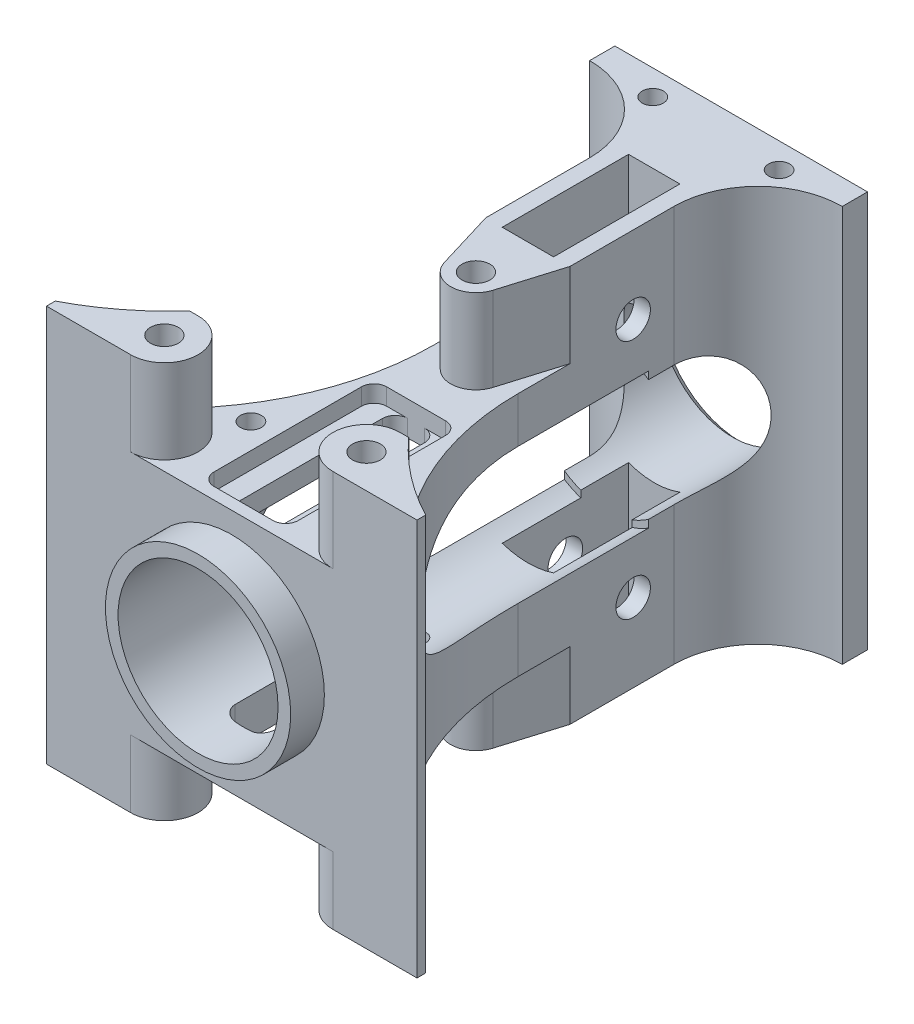
SolidWorks part; units mm, degrees
material "6061 合金"
ref_plane "前视基准面" through (0, 0, 0) normal (0, 0, 1) x (1, 0, 0)
ref_plane "上视基准面" through (0, 0, 0) normal (0, 1, 0) x (1, 0, 0)
ref_plane "右视基准面" through (0, 0, 0) normal (1, 0, 0) x (0, 0, -1)
sketch "草图1" plane through (0, 0, 0) normal (0, 0, 1) x (1, 0, 0)
  line L1 (-24, -15.5) -> (24, -15.5)
  line L2 (-24, -15.5) -> (-24, 15.5)
  line L3 (-24, 15.5) -> (24, 15.5)
  line L4 (24, -15.5) -> (24, 15.5)
  line L5 (0, 15.5) -> (0, -15.5) construction
  line L6 (-24, 0) -> (24, 0) construction
  point P0 (0, 0)
  dimension "D1" = 48
  dimension "D2" = 31
extrude "凸台-拉伸1" add sketch "草图1" along normal blind 39 and the other way blind 31.5
sketch "草图2" plane through (0, 0, -31.5) normal (0, 0, -1) x (-1, 0, 0)
  circle A0 centre (0, 0) radius 8.75
  dimension "D1" = 17.5
extrude "切除-拉伸1" cut sketch "草图2" against normal blind 135
sketch "草图4" plane through (0, 0, 39) normal (0, 0, 1) x (1, 0, 0)
  circle A0 centre (0, 0) radius 9.5
  dimension "D1" = 19
extrude "切除-拉伸2" cut sketch "草图4" against normal offset from surface (54.5 mm away) 16 up to face at (-8.75, 0, -31.5)
sketch "草图5" plane through (0, 15.5, 0) normal (0, 1, 0) x (1, 0, 0)
  line L0 (-36.5, 0) -> (36.5, 0) construction
  circle A0 centre (36.5, 0) radius 30 construction
  circle A1 centre (-36.5, 0) radius 30 construction
  circle A2 centre (36.5, 0) radius 31.5
  circle A3 centre (-36.5, 0) radius 31.5
  point P4 (0, 0)
  dimension "D1" = 60
  dimension "D2" = 73
  dimension "D3" = 1.5
extrude "切除-拉伸3" cut sketch "草图5" against normal blind 86
sketch "草图8" plane through (0, 0, 39) normal (0, 0, 1) x (1, 0, 0)
  circle A0 centre (0, 0) radius 10.5
  dimension "D1" = 21
extrude "切除-拉伸5" cut sketch "草图8" against normal blind 10 flip side to cut
ref_plane "基准面1" through (22, 0, 0) normal (1, 0, 0) x (0, 0, -1)
sketch "配合草图" plane through (0, 15.5, 0) normal (0, 1, 0) x (1, 0, 0)
  line L0 (-36.5, 0) -> (36.5, 0) construction
  circle A0 centre (36.5, 0) radius 30
  circle A1 centre (-36.5, 0) radius 30
  point P4 (0, 0)
  dimension "D2" = 60
  dimension "D1" = 73
sketch "草图12" plane through (0, 15.5, 0) normal (0, 1, 0) x (1, 0, 0)
  line L7 (0, 0) -> (0, 33.1497) construction
  line L16 (-5, 0) -> (-5, 18.5)
  line L17 (-5, 0) -> (-24, 28.9137)
  line L20 (-24, 28.9137) -> (-24, 31.5)
  line L22 (-24, 31.5) -> (-15, 31.5)
  line L25 (-15, 31.5) -> (-15, 28.5)
  line L32 (15, 28.5) -> (23.0263, 27) construction
  line L33 (15, 31.5) -> (15, 28.5)
  line L34 (24, 31.5) -> (15, 31.5)
  line L35 (24, 28.9137) -> (24, 31.5)
  line L36 (5, 0) -> (24, 28.9137)
  line L37 (5, 0) -> (5, 18.5)
  arc A5 (-24, -28.9137) -> (-24, 28.9137) centre (-36.5, 0) ccw construction
  arc A8 (-15, 28.5) -> (-5, 18.5) centre (-15, 18.5) cw
  arc A9 (15, 28.5) -> (5, 18.5) centre (15, 18.5) ccw
  dimension "D3" = 10
  dimension "D1" = 15
  dimension "D2" = 3
extrude "切除-拉伸6" cut sketch "草图12" against normal blind 50
sketch "草图14" plane through (22, 0, 0) normal (1, 0, 0) x (0, 0, -1)
  line L0 (31.5, -15.5) -> (31.5, 15.5) construction
  line L1 (-31.5, -15.5) -> (31.5, -15.5)
  line L2 (-31.5, -15.5) -> (-31.5, 15.5)
  line L3 (-31.5, 15.5) -> (31.5, 15.5)
  line L4 (31.5, -15.5) -> (31.5, 15.5)
  line L5 (0, 15.5) -> (0, -15.5) construction
  line L6 (-31.5, 0) -> (31.5, 0) construction
  line L7 (-29, 15.5) -> (-28.9137, 15.5) construction
  point P0 (0, 0)
extrude "切除-拉伸7" cut sketch "草图14" along normal blind 50
mirror "镜向1" about plane through (0, 0, 0) normal (1, 0, 0) of "切除-拉伸7"
sketch "草图15" plane through (-22, 0, 0) normal (-1, 0, 0) x (0, 0, 1)
  line L0 (29, 15.5) -> (38, 15.5)
  line L1 (38, 15.5) -> (38, -15.5)
  line L2 (38, -15.5) -> (29, -15.5)
  line L3 (29, 15.5) -> (29, -15.5)
  dimension "D1" = 9
extrude "凸台-拉伸2" add sketch "草图15" against normal blind 2
sketch "草图16" plane through (-22, 0, 0) normal (-1, 0, 0) x (0, 0, 1)
  line L0 (30.2, -7) -> (33.1, -7) construction
  line L1 (30.2, 13) -> (35.3014, 13) construction
  line L2 (29, -7) -> (38, -7)
  line L3 (29, 13) -> (38, 13)
  line L5 (38, -15.5) -> (38, 15.5) construction
  line L6 (29, -7) -> (29, -15.5)
  line L7 (38, -15.5) -> (27.9643, -15.5) construction
  line L8 (29, -15.5) -> (38, -15.5)
  line L9 (38, -15.5) -> (38, -7)
  line L10 (29, 13) -> (29, 15.5)
  line L11 (27.9643, 15.5) -> (38, 15.5) construction
  line L12 (29, 15.5) -> (38, 15.5)
  line L13 (38, 15.5) -> (38, 13)
  line L14 (29, 15.5) -> (29, -15.5) construction
extrude "切除-拉伸8" cut sketch "草图16" against normal blind 3
fillet "圆角1" radius 3.5 2 edges at (-21, -7, 38) (-21, 13, 38)
sketch "草图17" plane through (-22, 0, 0) normal (-1, 0, 0) x (0, 0, 1)
  line L0 (29, 13) -> (34.5, 13) construction
  line L2 (34.5, -7) -> (29, -7) construction
  circle A4 centre (35.2, 9.8) radius 1.55
  circle A5 centre (35.2, -3.8) radius 1.55
  dimension "D1" = 3.1
  dimension "D2" = 3.2
  dimension "D3" = 35.2
  dimension "D4" = 35.2
  dimension "D5" = 3.2
extrude "切除-拉伸9" cut sketch "草图17" against normal blind 3
fillet "圆角2" [suppressed] radius 0.5
sketch "草图18" plane through (22, 0, 0) normal (1, 0, 0) x (0, 0, -1)
  line L4 (-38, 9.5) -> (-38, -3.5)
  line L5 (-34.5, -7) -> (-29, -7)
  line L6 (-29, -7) -> (-29, 13)
  line L7 (-29, 13) -> (-34.5, 13)
  line L8 (-38, 9.5) -> (-38, -3.5)
  line L9 (-34.5, -7) -> (-29, -7)
  line L10 (-29, -7) -> (-29, 13)
  line L11 (-29, 13) -> (-34.5, 13)
  circle A0 centre (-35.2, -3.8) radius 1.55 construction
  circle A1 centre (-35.2, 9.8) radius 1.55 construction
  arc A2 (-38, -3.5) -> (-34.5, -7) centre (-34.5, -3.5) ccw
  arc A3 (-34.5, 13) -> (-38, 9.5) centre (-34.5, 9.5) ccw
  arc A4 (-38, -3.5) -> (-34.5, -7) centre (-34.5, -3.5) ccw
  arc A5 (-34.5, 13) -> (-38, 9.5) centre (-34.5, 9.5) ccw
  circle A6 centre (-35.2, -3.8) radius 1.55
  circle A7 centre (-35.2, 9.8) radius 1.55
  dimension "D1" = 0
extrude "凸台-拉伸3" add sketch "草图18" against normal blind 2
sketch "草图19" plane through (0, 15.5, 0) normal (0, 1, 0) x (1, 0, 0)
  line L7 (5, 0) -> (5, 18.5)
  line L8 (-22, -27.9643) -> (-22, -29)
  line L9 (-22, -29) -> (22, -29)
  line L10 (22, -29) -> (22, -27.9643)
  line L13 (15, 31.5) -> (-15, 31.5)
  line L14 (-15, 31.5) -> (-15, 28.5)
  line L15 (-5, 18.5) -> (-5, 0)
  line L16 (-22, -27.9643) -> (-22, -29)
  line L17 (-22, -29) -> (22, -29)
  line L18 (22, -29) -> (22, -27.9643)
  line L21 (15, 31.5) -> (-15, 31.5)
  line L22 (-15, 31.5) -> (-15, 28.5)
  line L23 (-5, 18.5) -> (-5, 0)
  line L24 (5, 0) -> (5, 18.5)
  line L25 (15, 28.5) -> (15, 31.5)
  line L26 (15, 28.5) -> (15, 31.5)
  arc A4 (5, 0) -> (22, -27.9643) centre (36.5, 0) ccw
  arc A5 (15, 28.5) -> (5, 18.5) centre (15, 18.5) ccw
  arc A6 (-5, 18.5) -> (-15, 28.5) centre (-15, 18.5) ccw
  arc A7 (-22, -27.9643) -> (-5, 0) centre (-36.5, 0) ccw
  arc A8 (5, 0) -> (22, -27.9643) centre (36.5, 0) ccw
  arc A10 (-5, 18.5) -> (-15, 28.5) centre (-15, 18.5) ccw
  arc A11 (-22, -27.9643) -> (-5, 0) centre (-36.5, 0) ccw
  arc A12 (15, 28.5) -> (5, 18.5) centre (15, 18.5) ccw
  dimension "D1" = 0
extrude "凸台-拉伸4" add sketch "草图19" along normal blind 8
sketch "草图20" plane through (0, 0, 0) normal (1, 0, 0) x (0, 0, -1)
  circle A0 centre (13.67, 14.3) radius 2.05
  dimension "D3" = 4.1
  dimension "D1" = 13.67
  dimension "D2" = 14.3
extrude "切除-拉伸10" cut sketch "草图20" against normal mid plane 78
sketch "草图21" plane through (0, -15.5, 0) normal (0, -1, 0) x (1, 0, 0)
  line L8 (22, 29) -> (-22, 29)
  line L9 (-22, 29) -> (-22, 27.9643)
  line L10 (-5, 0) -> (-5, -18.5)
  line L11 (-15, -28.5) -> (-15, -31.5)
  line L12 (-15, -31.5) -> (15, -31.5)
  line L13 (15, -31.5) -> (15, -28.5)
  line L14 (5, -18.5) -> (5, 0)
  line L15 (22, 27.9643) -> (22, 29)
  line L16 (22, 29) -> (-22, 29)
  line L17 (-22, 29) -> (-22, 27.9643)
  line L18 (-5, 0) -> (-5, -18.5)
  line L19 (-15, -28.5) -> (-15, -31.5)
  line L20 (-15, -31.5) -> (15, -31.5)
  line L21 (15, -31.5) -> (15, -28.5)
  line L22 (5, -18.5) -> (5, 0)
  line L23 (22, 27.9643) -> (22, 29)
  arc A4 (-5, 0) -> (-22, 27.9643) centre (-36.5, 0) ccw
  arc A5 (-15, -28.5) -> (-5, -18.5) centre (-15, -18.5) ccw
  arc A6 (5, -18.5) -> (15, -28.5) centre (15, -18.5) ccw
  arc A7 (22, 27.9643) -> (5, 0) centre (36.5, 0) ccw
  arc A8 (-5, 0) -> (-22, 27.9643) centre (-36.5, 0) ccw
  arc A9 (-15, -28.5) -> (-5, -18.5) centre (-15, -18.5) ccw
  arc A10 (5, -18.5) -> (15, -28.5) centre (15, -18.5) ccw
  arc A11 (22, 27.9643) -> (5, 0) centre (36.5, 0) ccw
  dimension "D1" = 0
extrude "凸台-拉伸5" add sketch "草图21" along normal blind 8.1
mirror "镜向6" about plane through (0, 0, 0) normal (0, 1, 0) of "切除-拉伸10"
sketch "草图23" plane through (0, 0, 0) normal (1, 0, 0) x (0, 0, -1)
  line L0 (18.5, -23.6) -> (0, -23.6) construction
  line L1 (6.17, -23.6) -> (21.17, -23.6)
  line L2 (6.17, -23.6) -> (6.17, 52.2)
  line L3 (6.17, 52.2) -> (21.17, 52.2)
  line L4 (21.17, -23.6) -> (21.17, 52.2)
  line L5 (13.67, 52.2) -> (13.67, -23.6) construction
  line L6 (6.17, 14.3) -> (21.17, 14.3) construction
  point P0 (13.67, 14.3)
  dimension "D1" = 15
extrude "切除-拉伸11" cut sketch "草图23" against normal mid plane 6.1
sketch "草图24" plane through (0, 23.5, 0) normal (0, 1, 0) x (1, 0, 0)
  line L0 (-7.5, 28.5) -> (7.5, 28.5) construction
  line L1 (0, 28.5) -> (0, 0) construction
  line L2 (15, 31.5) -> (-15, 31.5) construction
  point P3 (0, 28.5)
  dimension "D1" = 3
  dimension "D2" = 15
hole_wizard "M3 螺纹孔1" positions "草图25" profile "草图26" tap size "M3" standard "GB"
sketch "草图25" plane through (0, 23.5, 0) normal (0, 1, 0) x (1, 0, 0)
  point P0 (-7.5, 28.5)
  point P3 (7.5, 28.5)
sketch "草图26" plane through (-7.5, 23.5, -28.5) normal (1, 0, 0) x (0, 0, 1)
  line L0 (0, 0) -> (0, 8.2511)
  line L1 (0, 8.2511) -> (1.25, 7.5)
  line L2 (1.25, 7.5) -> (1.25, 0)
  line L5 (1.25, 0) -> (0, 0)
  line L10 (0, 8.2511) -> (-1.25, 7.5) construction
  line L11 (0, -6.35) -> (0, 107.95) construction
  dimension "螺纹孔钻头直径" = 2.5
  dimension "螺纹孔钻头深度" = 7.5
  dimension "导头角度" = 118
cosmetic thread "孔螺蚊线1"
cosmetic thread "孔螺蚊线2"
sketch "草图27" plane through (0, 23.5, 0) normal (0, 1, 0) x (1, 0, 0)
  line L0 (-12, -25) -> (12, -25) construction
  line L1 (0, 0) -> (0, -25) construction
  line L2 (-22, -29) -> (22, -29) construction
  point P3 (0, -25)
  dimension "D1" = 4
  dimension "D2" = 24
hole_wizard "M4 螺纹孔2" positions "草图28" profile "草图29" tap size "M4" standard "GB"
sketch "草图28" plane through (0, 23.5, 0) normal (0, 1, 0) x (1, 0, 0)
  point P0 (-12, -25)
  point P3 (12, -25)
sketch "草图29" plane through (-12, 23.5, 25) normal (1, 0, 0) x (0, 0, 1)
  line L0 (0, 0) -> (0, 11.0914)
  line L1 (0, 11.0914) -> (1.65, 10.1)
  line L2 (1.65, 10.1) -> (1.65, 0)
  line L5 (1.65, 0) -> (0, 0)
  line L10 (0, 11.0914) -> (-1.65, 10.1) construction
  line L11 (0, -6.35) -> (0, 107.95) construction
  dimension "螺纹孔钻头直径" = 3.3
  dimension "螺纹孔钻头深度" = 10.1
  dimension "导头角度" = 118
cosmetic thread "孔螺蚊线3"
cosmetic thread "孔螺蚊线4"
sketch "草图30" plane through (0, 23.5, 0) normal (0, 1, 0) x (1, 0, 0)
  line L0 (-10.5, -29) -> (10.5, -29) construction
  line L1 (-12, -21) -> (-13.0213, -21)
  line L2 (12, -21) -> (13.0213, -21)
  line L3 (-12, -29) -> (12, -29)
  line L4 (-5, 0) -> (5, 0)
  arc A0 (-12, -29) -> (-12, -21) centre (-12, -25) ccw
  arc A1 (12, -21) -> (12, -29) centre (12, -25) ccw
  arc A2 (-22, -27.9643) -> (-5, 0) centre (-36.5, 0) ccw construction
  arc A3 (5, 0) -> (22, -27.9643) centre (36.5, 0) ccw construction
  arc A4 (5, 0) -> (13.0213, -21) centre (36.5, 0) ccw
  arc A5 (-13.0213, -21) -> (-5, 0) centre (-36.5, 0) ccw
extrude "切除-拉伸12" cut sketch "草图30" against normal blind 10
hole_wizard "M3 螺纹孔2" positions "草图31" profile "草图32" tap size "M3" standard "GB"
sketch "草图31" plane through (0, -23.6, 0) normal (0, -1, 0) x (-1, 0, 0)
  point P6 (-7.5, 28.5)
  point P9 (7.5, 28.5)
sketch "草图32" plane through (7.5, -23.6, -28.5) normal (1, 0, 0) x (0, 0, -1)
  line L0 (0, 0) -> (0, 8.2511)
  line L1 (0, 8.2511) -> (1.25, 7.5)
  line L2 (1.25, 7.5) -> (1.25, 0)
  line L5 (1.25, 0) -> (0, 0)
  line L10 (0, 8.2511) -> (-1.25, 7.5) construction
  line L11 (0, -6.35) -> (0, 107.95) construction
  dimension "螺纹孔钻头直径" = 2.5
  dimension "螺纹孔钻头深度" = 7.5
  dimension "导头角度" = 118
cosmetic thread "孔螺蚊线5"
cosmetic thread "孔螺蚊线6"
extrude "切除-拉伸13" cut sketch "草图30<2>" along normal blind 8 from surface starting at face at (7.5, -23.6, -29.75)
sketch "草图30<2>" plane through (0, 23.5, 0) normal (0, 1, 0) x (1, 0, 0) same geometry as "草图30"
sketch "草图33" plane through (5, 0, 0) normal (1, 0, 0) x (0, 0, -1)
  line L0 (0, -15.6) -> (6.17, -15.6)
  line L1 (6.17, -15.6) -> (6.17, -23.6)
  line L2 (18.5, -23.6) -> (0, -23.6) construction
  line L3 (6.17, -23.6) -> (0, -23.6)
  line L4 (0, -23.6) -> (0, -15.6)
  line L5 (0, 13.5) -> (0, 23.5)
  line L6 (0, 23.5) -> (6.17, 23.5)
  line L8 (0, 23.5) -> (18.5, 23.5) construction
  line L9 (6.17, 23.5) -> (6.17, 13.5)
  line L10 (6.17, 13.5) -> (0, 13.5)
  line L11 (6.17, -8.9971) -> (6.17, -23.6) construction
extrude "切除-拉伸14" cut sketch "草图33" against normal blind 36
chamfer "倒角1" distance 1 angle 45 1 edges at (-8.75, 0, -31.5)
hole_wizard "M4 螺纹孔4" positions "草图34" profile "草图35" tap size "M4" standard "GB"
sketch "草图34" plane through (0, -23.6, 0) normal (0, -1, 0) x (-1, 0, 0)
  point P0 (-12, -25)
  point P3 (12, -25)
sketch "草图35" plane through (12, -23.6, 25) normal (1, 0, 0) x (0, 0, -1)
  line L0 (0, 0) -> (0, 11.0914)
  line L1 (0, 11.0914) -> (1.65, 10.1)
  line L2 (1.65, 10.1) -> (1.65, 0)
  line L5 (1.65, 0) -> (0, 0)
  line L10 (0, 11.0914) -> (-1.65, 10.1) construction
  line L11 (0, -6.35) -> (0, 107.95) construction
  dimension "螺纹孔钻头直径" = 3.3
  dimension "螺纹孔钻头深度" = 10.1
  dimension "导头角度" = 118
cosmetic thread "孔螺蚊线9"
cosmetic thread "孔螺蚊线10"
sketch "草图36" plane through (0, 13.5, 0) normal (0, 1, 0) x (1, 0, 0)
  line L0 (0, 0) -> (0, -17.35) construction
  line L1 (-5, -27.6) -> (5, -27.6)
  line L2 (-5, -27.6) -> (-5, -7.1)
  line L3 (-5, -7.1) -> (5, -7.1)
  line L4 (5, -27.6) -> (5, -7.1)
  line L5 (-5, -27.6) -> (5, -7.1) construction
  line L6 (-5, -7.1) -> (5, -27.6) construction
  line L7 (-12, -29) -> (12, -29) construction
  point P3 (0, -17.35)
  dimension "D1" = 10
  dimension "D2" = 20.5
  dimension "D3" = 1.4
extrude "切除-拉伸15" cut sketch "草图36" against normal blind 2
sketch "草图37" plane through (0, 11.5, 0) normal (0, 1, 0) x (1, 0, 0)
  line L0 (5, -7.1) -> (-5, -7.1) construction
  line L1 (-2.5, -27.6) -> (2.5, -27.6)
  line L2 (-2.5, -27.6) -> (-2.5, -7.1)
  line L3 (-2.5, -7.1) -> (2.5, -7.1)
  line L4 (2.5, -27.6) -> (2.5, -7.1)
  line L5 (-2.5, -27.6) -> (2.5, -7.1) construction
  line L6 (-2.5, -7.1) -> (2.5, -27.6) construction
  line L7 (0, 0) -> (0, -17.35) construction
  line L8 (-5, -27.6) -> (5, -27.6) construction
  point P0 (0, -17.35)
  dimension "D1" = 5
extrude "切除-拉伸17" cut sketch "草图37" against normal blind 72
fillet "圆角3" radius 1.5 8 edges at (-2.5, 10.3326, 27.6) (-5, 12.5, 27.6) (-2.5, 10.3326, 7.1) (-5, 12.5, 7.1) (2.5, 10.3326, 7.1) (2.5, 10.3326, 27.6) (5, 12.5, 27.6) (5, 12.5, 7.1)
sketch "草图38" plane through (0, -15.6, 0) normal (0, -1, 0) x (1, 0, 0)
  line L0 (-2.5, 27.6) -> (2.5, 27.6) construction
  line L1 (-5, 7.1) -> (5, 7.1)
  line L2 (-5, 7.1) -> (-5, 27.6)
  line L3 (-5, 27.6) -> (5, 27.6)
  line L4 (5, 7.1) -> (5, 27.6)
  line L5 (-5, 7.1) -> (5, 27.6) construction
  line L6 (-5, 27.6) -> (5, 7.1) construction
  line L7 (2.5, 7.1) -> (-2.5, 7.1) construction
  line L8 (0, 17.35) -> (0, 0) construction
  point P0 (0, 17.35)
  dimension "D1" = 10
extrude "切除-拉伸18" cut sketch "草图38" against normal blind 2
fillet "圆角4" radius 1.5 8 edges at (-2.5, -11.3826, 7.1) (-2.5, -11.3826, 27.6) (2.5, -11.3826, 7.1) (2.5, -11.3826, 27.6) (5, -14.6, 27.6) (5, -14.6, 7.1) (-5, -14.6, 27.6) (-5, -14.6, 7.1)
sketch "草图39" plane through (0, 13.5, 0) normal (0, 1, 0) x (1, 0, 0)
  line L0 (-8, -18.7232) -> (8, -18.7232) construction
  line L1 (0, 0) -> (0, -18.7232) construction
  line L2 (5, -26.1) -> (5, -8.6) construction
  circle A0 centre (8, -18.7232) radius 1.55 construction
  arc A12 (5, 0) -> (13.0213, -21) centre (36.5, 0) ccw construction
  dimension "D1" = 3.1
  dimension "D3" = 2.6
  dimension "D2" = 3
hole_wizard "M3 螺纹孔3" positions "草图40" profile "草图41" tap size "M3" standard "GB"
sketch "草图40" plane through (0, 13.5, 0) normal (0, 1, 0) x (1, 0, 0)
  point P0 (-8, -18.7232)
  point P3 (8, -18.7232)
sketch "草图41" plane through (-8, 13.5, 18.7232) normal (1, 0, 0) x (0, 0, 1)
  line L0 (0, 0) -> (0, 6.2511)
  line L1 (0, 6.2511) -> (1.25, 5.5)
  line L2 (1.25, 5.5) -> (1.25, 0)
  line L5 (1.25, 0) -> (0, 0)
  line L10 (0, 6.2511) -> (-1.25, 5.5) construction
  line L11 (0, -6.35) -> (0, 107.95) construction
  dimension "螺纹孔钻头直径" = 2.5
  dimension "螺纹孔钻头深度" = 5.5
  dimension "导头角度" = 118
cosmetic thread "孔螺蚊线11"
cosmetic thread "孔螺蚊线12"
hole_wizard "M3 螺纹孔4" positions "草图43" profile "草图44" tap size "M3" standard "GB"
sketch "草图43" plane through (0, -15.6, 0) normal (0, -1, 0) x (-1, 0, 0)
  point P0 (8, -18.7232)
  point P3 (-8, -18.7232)
sketch "草图44" plane through (-8, -15.6, 18.7232) normal (1, 0, 0) x (0, 0, -1)
  line L0 (0, 0) -> (0, 6.2511)
  line L1 (0, 6.2511) -> (1.25, 5.5)
  line L2 (1.25, 5.5) -> (1.25, 0)
  line L5 (1.25, 0) -> (0, 0)
  line L10 (0, 6.2511) -> (-1.25, 5.5) construction
  line L11 (0, -6.35) -> (0, 107.95) construction
  dimension "螺纹孔钻头直径" = 2.5
  dimension "螺纹孔钻头深度" = 5.5
  dimension "导头角度" = 118
cosmetic thread "孔螺蚊线13"
cosmetic thread "孔螺蚊线14"
sketch "草图45" plane through (0, 13.5, 0) normal (0, 1, 0) x (1, 0, 0)
  line L0 (22, -29) -> (22, -34.5) construction
  line L1 (-22, -29) -> (22, -29)
  line L2 (-22, -29) -> (-22, -44)
  line L3 (-22, -44) -> (22, -44)
  line L4 (22, -29) -> (22, -44)
  dimension "D1" = 15
extrude "切除-拉伸19" cut sketch "草图45" against normal blind 37
sketch "草图47" plane through (0, -15.6, 0) normal (0, -1, 0) x (1, 0, 0)
  line L0 (-5, -6.17) -> (-2.8716, 0.8684)
  line L1 (2.8716, 0.8684) -> (5, -6.17)
  line L2 (-5, -6.17) -> (5, -6.17)
  arc A0 (2.8716, 0.8684) -> (-2.8716, 0.8684) centre (0, 0) ccw
  dimension "D1" = 6
extrude "凸台-拉伸6" add sketch "草图47" along normal up to surface (8 mm away) up to face at (-12, -23.6, 23.35)
hole_wizard "M4 螺纹孔5" positions "草图48" profile "草图49" tap size "M4" standard "GB"
sketch "草图48" plane through (0, -23.6, 0) normal (0, -1, 0) x (-1, 0, 0)
  point P0 (0, 0)
sketch "草图49" plane through (0, -23.6, 0) normal (1, 0, 0) x (0, 0, -1)
  line L0 (0, 0) -> (0, 11.0914)
  line L1 (0, 11.0914) -> (1.65, 10.1)
  line L2 (1.65, 10.1) -> (1.65, 0)
  line L5 (1.65, 0) -> (0, 0)
  line L10 (0, 11.0914) -> (-1.65, 10.1) construction
  line L11 (0, -6.35) -> (0, 107.95) construction
  dimension "螺纹孔钻头直径" = 3.3
  dimension "螺纹孔钻头深度" = 10.1
  dimension "导头角度" = 118
cosmetic thread "孔螺蚊线15"
sketch "草图50" plane through (0, 13.5, 0) normal (0, 1, 0) x (1, 0, 0)
  line L0 (-5, 6.17) -> (-2.8716, -0.8684)
  line L1 (5, 6.17) -> (2.8716, -0.8684)
  line L2 (-5, 6.17) -> (5, 6.17)
  arc A0 (-2.8716, -0.8684) -> (2.8716, -0.8684) centre (0, 0) ccw
  arc A1 (-2.8716, -0.8684) -> (2.8716, -0.8684) centre (0, 0) ccw construction
extrude "凸台-拉伸7" add sketch "草图50" along normal up to surface (10 mm away) up to face at (15.3409, 23.5, 25.6745)
hole_wizard "M4 螺纹孔6" positions "草图51" profile "草图52" tap size "M4" standard "GB"
sketch "草图51" plane through (0, 23.5, 0) normal (0, 1, 0) x (1, 0, 0)
  point P0 (0, 0)
sketch "草图52" plane through (0, 23.5, 0) normal (1, 0, 0) x (0, 0, 1)
  line L0 (0, 0) -> (0, 11.0914)
  line L1 (0, 11.0914) -> (1.65, 10.1)
  line L2 (1.65, 10.1) -> (1.65, 0)
  line L5 (1.65, 0) -> (0, 0)
  line L10 (0, 11.0914) -> (-1.65, 10.1) construction
  line L11 (0, -6.35) -> (0, 107.95) construction
  dimension "螺纹孔钻头直径" = 3.3
  dimension "螺纹孔钻头深度" = 10.1
  dimension "导头角度" = 118
cosmetic thread "孔螺蚊线16"
sketch "草图53" plane through (0, 0, 29) normal (0, 0, 1) x (1, 0, 0)
  circle A0 centre (0, 0) radius 9.5
  circle A1 centre (0, 0) radius 9.5 construction
  circle A2 centre (0, 0) radius 11
  dimension "D1" = 1.5
extrude "凸台-拉伸8" add sketch "草图53" along normal blind 4
